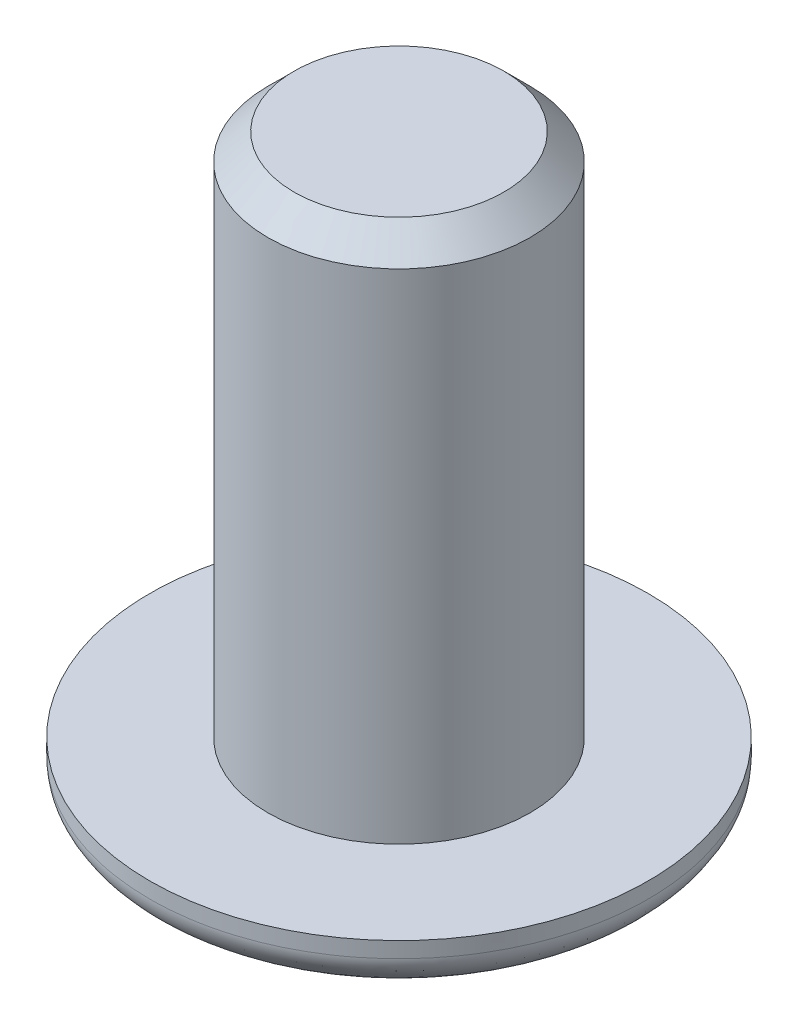
SolidWorks part; units mm, degrees
material "ASTM A36 钢"
ref_plane "前视基准面" through (0, 0, 0) normal (0, 0, 1) x (1, 0, 0)
ref_plane "上视基准面" through (0, 0, 0) normal (0, 1, 0) x (1, 0, 0)
ref_plane "右视基准面" through (0, 0, 0) normal (1, 0, 0) x (0, 0, -1)
sketch "草图1" plane through (0, 0, 0) normal (0, 1, 0) x (1, 0, 0)
  line L1 (0, -1.7321) -> (1.5, -0.866)
  line L2 (1.5, -0.866) -> (1.5, 0.866)
  line L3 (1.5, 0.866) -> (0, 1.7321)
  line L4 (0, 1.7321) -> (-1.5, 0.866)
  line L5 (-1.5, 0.866) -> (-1.5, -0.866)
  line L6 (-1.5, -0.866) -> (0, -1.7321)
  circle A0 centre (0, 0) radius 1.5 construction
  circle A1 centre (0, 0) radius 4.75
extrude "凸台-拉伸1" add sketch "草图1" along normal blind 1.3
sketch "草图2" plane through (0, 1.3, 0) normal (0, 1, 0) x (1, 0, 0)
  circle A0 centre (0, 0) radius 2.5
extrude "凸台-拉伸2" add sketch "草图2" along normal blind 10
chamfer "倒角1" distance 0.5 angle 45 1 edges at (0, 11.3, 2.5)
fillet "圆角1" radius 2 1 edges at (0, 0, 4.75) second distance 1 first distance on face at (0, 0, 4.75)
